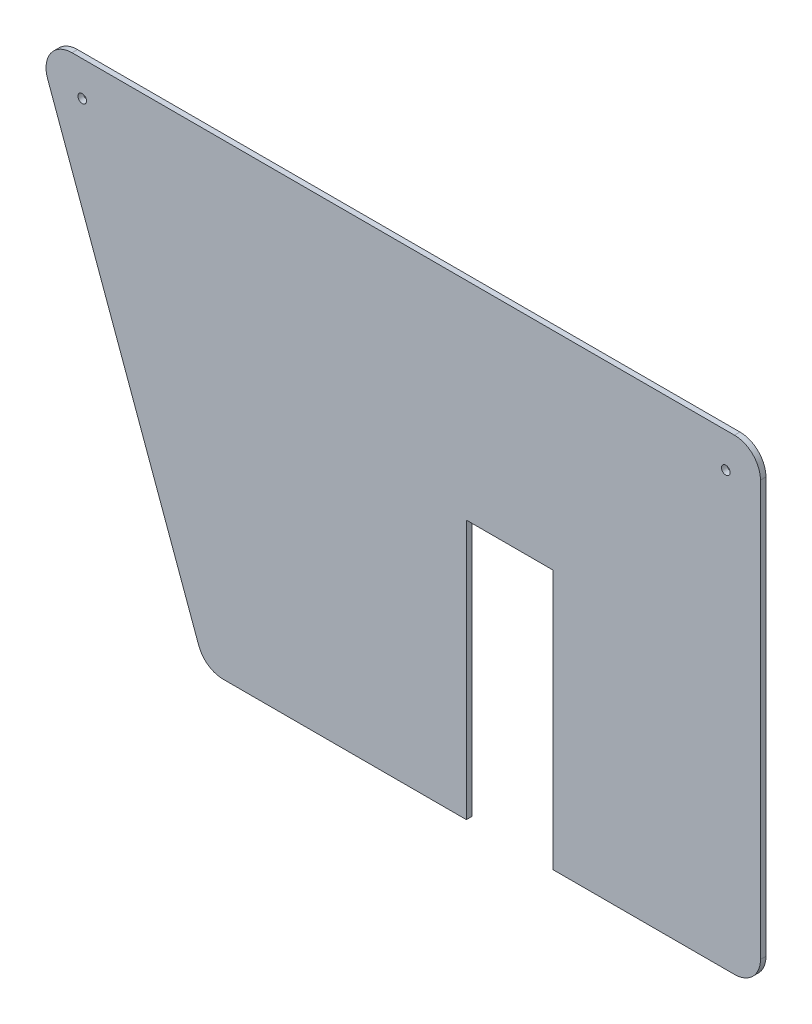
SolidWorks part; units mm, degrees
ref_plane "Front Plane" through (0, 0, 0) normal (0, 0, 1) x (1, 0, 0)
ref_plane "Top Plane" through (0, 0, 0) normal (0, 1, 0) x (1, 0, 0)
ref_plane "Right Plane" through (0, 0, 0) normal (1, 0, 0) x (0, 0, -1)
sketch "Sketch1" plane through (0, 0, 0) normal (0, 0, 1) x (1, 0, 0)
  line L3 (0, 270) -> (0, 0)
  line L5 (0, 270) -> (-419.4263, 270)
  line L6 (-419.4263, 270) -> (-321.1544, 0)
  line L7 (-321.1544, 0) -> (0, 0)
  dimension "D4" = 419.4263
  dimension "D5" = 270
  dimension "D7" = 70
base flange "Base-Flange1" sketch "Sketch1" thickness 3.175 reverse thickness direction no parameters "D1"=0.7366
fillet "Fillet1" radius 15 4 edges at (0, 0, -1.5875) (0, 270, -1.5875) (-321.1544, 0, -1.5875) (-419.4263, 270, -1.5875)
sketch "Sketch2" plane through (0, 0, -3.175) normal (0, 0, -1) x (-1, 0, 0)
  line L0 (120, 0) -> (120, 150)
  line L1 (310.6513, 0) -> (15, 0) construction
  line L2 (120, 150) -> (170, 150)
  line L3 (170, 150) -> (170, 0)
  line L4 (170, 0) -> (120, 0)
  line L5 (0, 15) -> (0, 255) construction
  dimension "D1" = 50
  dimension "D2" = 120
  dimension "D3" = 150
extrude "Cut-Extrude1" cut sketch "Sketch2" against normal blind 10 normal cut yes
sketch "Sketch3" plane through (0, 0, -3.175) normal (0, 0, -1) x (-1, 0, 0)
  line L0 (15, 270) -> (398.0041, 270) construction
  line L1 (0, 15) -> (0, 255) construction
  circle A0 centre (20, 250) radius 2.5
  circle A1 centre (392.0995, 250) radius 2.5
  dimension "D1" = 5
  dimension "D2" = 5
  dimension "D3" = 20
  dimension "D4" = 20
  dimension "D5" = 20
  dimension "D6" = 20
extrude "Cut-Extrude2" cut sketch "Sketch3" against normal blind 10 normal cut yes
sketch "Bend-Lines1" [suppressed] plane through (0, 0, 0) normal (0, 1, 0) x (1, 0, 0)
sketch "Bounding-Box1" [suppressed] plane through (0, 0, 0) normal (0, 1, 0) x (1, 0, 0)
sheet metal parameters "Sheet-Metal1" thickness 3.175 parameters "D1"=0.7366
flat pattern "Flat-Pattern1" [suppressed]
sketch "Bend-Lines2" plane through (0, 0, 0) normal (0, 1, 0) x (1, 0, 0)
sketch3d "Bounding-Box2" [suppressed]
  line L0 (-413.0041, 0, 0) -> (0, 0, 0) construction
  line L1 (-413.0041, 250.7055, 0) -> (0, 250.7055, 0) construction
  line L2 (-413.0041, 0, 0) -> (-413.0041, 250.7055, 0) construction
  line L3 (0, 0, 0) -> (0, 250.7055, 0) construction
sheet metal parameters "Sheet-Metal2" thickness 3.175 parameters "D1"=0.7366
flat pattern "Flat-Pattern1"
sketch "Bend-Lines2" plane through (0, 0, 0) normal (0, 1, 0) x (1, 0, 0)
sketch3d "Bounding-Box2" [suppressed]
  line L0 (-413.0041, 0, 0) -> (0, 0, 0) construction
  line L1 (-413.0041, 250.7055, 0) -> (0, 250.7055, 0) construction
  line L2 (-413.0041, 0, 0) -> (-413.0041, 250.7055, 0) construction
  line L3 (0, 0, 0) -> (0, 250.7055, 0) construction
sheet metal parameters "Sheet-Metal3" thickness 3.175 parameters "D1"=0.7366
flat pattern "Flat-Pattern1"
sketch "Bend-Lines2" plane through (0, 0, 0) normal (0, 1, 0) x (1, 0, 0)
sketch3d "Bounding-Box2" [suppressed]
  line L0 (-413.0041, 0, 0) -> (0, 0, 0) construction
  line L1 (-413.0041, 270, 0) -> (0, 270, 0) construction
  line L2 (-413.0041, 0, 0) -> (-413.0041, 270, 0) construction
  line L3 (0, 0, 0) -> (0, 270, 0) construction
